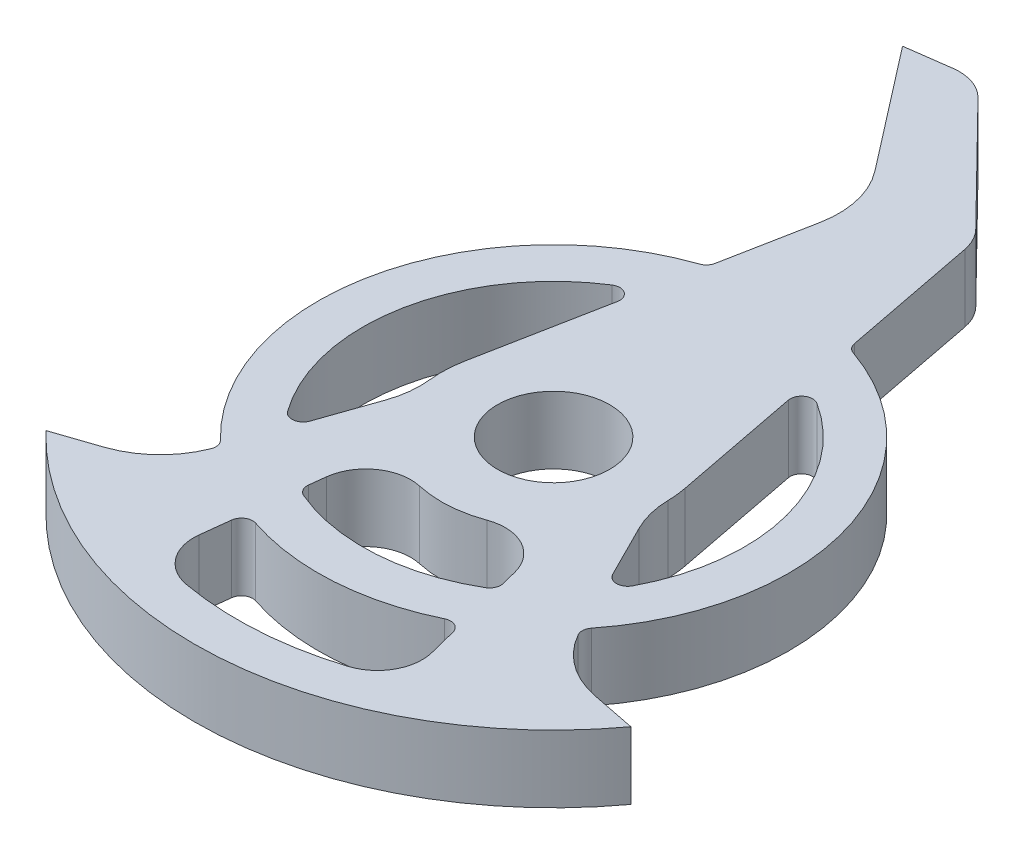
SolidWorks part; units mm, degrees
material "AISI Type A2 Tool Steel"
ref_plane "Front Plane" through (0, 0, 0) normal (0, 0, 1) x (1, 0, 0)
ref_plane "Top Plane" through (0, 0, 0) normal (0, 1, 0) x (1, 0, 0)
ref_plane "Right Plane" through (0, 0, 0) normal (1, 0, 0) x (0, 0, -1)
other "Center of Mass"
other "Bounding Box"
ref_plane "Default Plane" through (-8.9266, -12.7485, 0) normal (-0.1736, 0.9848, 0) x (0.9848, 0.1736, 0)
sketch "Sketch1" plane through (0, 0, 0) normal (0, 1, 0) x (1, 0, 0)
  line L0 (-15.5865, 3.0126) -> (-6.35, 50.8)
  line L1 (-6.35, 50.8) -> (-23.2013, 72.582)
  line L2 (15.5865, 3.0126) -> (6.35, 50.8)
  line L4 (-6.35, 50.8) -> (6.35, 50.8) construction
  line L5 (0, 50.8) -> (0, 0) construction
  line L6 (-23.2013, 72.582) -> (0, 0) construction
  line L7 (-23.2013, 72.582) -> (-13.7628, 73.8626)
  line L8 (-13.7628, 73.8626) -> (5.7363, 53.975)
  line L9 (5.7363, 53.975) -> (6.35, 50.8)
  circle A0 centre (0, 0) radius 7.9375
  arc A1 (-15.5865, 3.0126) -> (15.5865, 3.0126) centre (0, 0) ccw
  circle A2 centre (0, 0) radius 76.2 construction
  arc A4 (15.5865, 3.0126) -> (-15.5865, 3.0126) centre (0, 0) ccw construction
  dimension "D1" = 15.875
  dimension "D2" = 152.4
  dimension "D3" = 31.75
  dimension "D4" = 3.175
  dimension "D5" = 12.7
  dimension "D6" = 50.8
  dimension "D7" = 20
  dimension "D8" = 9.525
  dimension "D9" = 60
extrude "Boss-Extrude1" add sketch "Sketch1" along normal mid plane 9.525
fillet "Fillet6" radius 6.35 2 edges at (-13.7628, 0, -73.8626) (5.7363, 0, -53.975)
fillet "Fillet9" radius 12.7 1 edges at (-6.35, 0, -50.8)
sketch "Sketch4" plane through (0, 4.7625, 0) normal (0, 1, 0) x (1, 0, 0)
  circle A0 centre (0, 0) radius 33.3375
  circle A1 centre (0, 0) radius 26.9875
  dimension "D1" = 66.675
  dimension "D2" = 6.35
extrude "Boss-Extrude4" add sketch "Sketch4" against normal up to surface (9.525 mm away) up to face at (-6.3228, -4.7625, -45.9675)
sketch "Sketch2" plane through (0, 4.7625, 0) normal (0, 1, 0) x (1, 0, 0)
  line L0 (0, 0) -> (0, 50000) construction
  line L1 (-15.3133, -4.1855) -> (-24.6701, -31.0466)
  line L2 (-24.6701, -31.0466) -> (-36.6961, -35.1289)
  line L3 (15.7286, -2.1509) -> (28.5114, -27.5609)
  line L4 (28.5114, -27.5609) -> (40.9674, -30.0385)
  line L5 (3.3225, -50.6912) -> (0, 0) construction
  line L6 (-36.6961, -35.1289) -> (0, 0) construction
  line L7 (0, 0) -> (40.9674, -30.0385) construction
  line L8 (-36.6961, -35.1289) -> (2.1356, -32.5837) construction
  line L9 (2.1356, -32.5837) -> (40.9674, -30.0385) construction
  line L10 (-15.3133, -4.1855) -> (15.7286, -2.1509) construction
  line L11 (3.3225, -50.6912) -> (-3266.834, 49842.2549) construction
  arc A0 (-15.5865, 3.0126) -> (15.5865, 3.0126) centre (0, 0) ccw construction
  arc A1 (-36.6961, -35.1289) -> (40.9674, -30.0385) centre (0, 0) ccw
  circle A2 centre (0, 0) radius 76.2 construction
  arc A3 (-15.3133, -4.1855) -> (15.7286, -2.1509) centre (0, 0) ccw
  dimension "D1" = 25.4
  dimension "D2" = 25
  dimension "D3" = 25
  dimension "D4" = 100
  dimension "D5" = 3.175
  dimension "D6" = 12.7
  dimension "D7" = 3.75
extrude "Boss-Extrude2" add sketch "Sketch2" against normal up to surface (9.525 mm away) up to face at (-6.3228, -4.7625, -47.2253)
sketch "Sketch3" plane through (0, 4.7625, 0) normal (0, 1, 0) x (1, 0, 0)
  line L0 (-10.1613, -12.1969) -> (-11.5925, -24.3709)
  line L1 (11.6664, -10.7662) -> (14.6744, -22.6492)
  line L2 (-15.3133, -4.1855) -> (-10.1613, -12.1969) construction
  line L3 (11.6664, -10.7662) -> (15.7286, -2.1509) construction
  line L4 (-15.3133, -4.1855) -> (-20.1205, -17.9858) construction
  line L5 (-11.5925, -24.3709) -> (-12.367, -30.9588) construction
  line L6 (-12.367, -30.9588) -> (-13.7351, -42.5951)
  line L7 (14.6744, -22.6492) -> (16.3022, -29.0797) construction
  line L8 (16.3022, -29.0797) -> (19.1773, -40.4379)
  arc A0 (11.6664, -10.7662) -> (-10.1613, -12.1969) centre (0, 0) cw
  arc A1 (-15.5865, 3.0126) -> (15.5865, 3.0126) centre (0, 0) ccw construction
  arc A2 (-13.7351, -42.5951) -> (19.1773, -40.4379) centre (0, 0) ccw
  arc A4 (-11.5925, -24.3709) -> (14.6744, -22.6492) centre (0, 0) ccw
  arc A5 (-12.367, -30.9588) -> (16.3022, -29.0797) centre (0, 0) ccw
  arc A6 (25.4683, -21.5117) -> (10.0234, 31.795) centre (0, 0) ccw construction
  arc A7 (22.296, -15.2057) -> (11.4449, 24.4405) centre (0, 0) ccw construction
  arc A8 (-36.6961, -35.1289) -> (40.9674, -30.0385) centre (0, 0) ccw construction
  point P10 (-14.0206, -45.0242)
  dimension "D1" = 6.0452
  dimension "D2" = 12.5
  dimension "D3" = 9.525
extrude "Cut-Extrude1" cut sketch "Sketch3" against normal through all
fillet "Fillet7" radius 6.35 4 edges at (11.6664, 0, 10.7662) (-10.1613, 0, 12.1969) (19.1773, 0, 40.4379) (-13.7351, 0, 42.5951)
fillet "Fillet8" radius 12.7 4 edges at (28.5114, 0, 27.5609) (15.7286, 0, 2.1509) (-15.3133, 0, 4.1855) (-24.6701, 0, 31.0466)
fillet "Fillet10" radius 1.5875 12 edges at (-11.5925, 0, 24.3709) (-12.367, 0, 30.9588) (16.3022, 0, 29.0797) (25.4683, 0, 21.5117) (14.6744, 0, 22.6492) (22.296, 0, 15.2057) (11.4449, 0, -24.4405) (10.0234, 0, -31.795) (-11.4449, 0, -24.4405) (-10.0234, 0, -31.795) (-20.1205, 0, 17.9858) (-22.4426, 0, 24.652)
